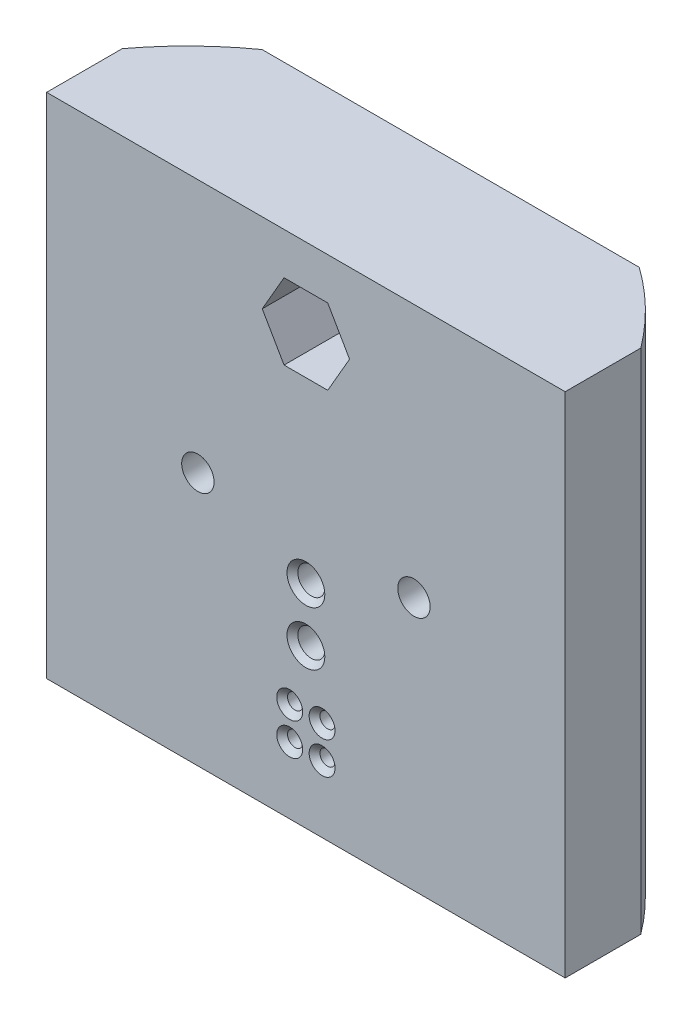
SolidWorks part; units mm, degrees
ref_plane "Front Plane" through (0, 0, 0) normal (0, 0, 1) x (1, 0, 0)
ref_plane "Top Plane" through (0, 0, 0) normal (0, 1, 0) x (1, 0, 0)
ref_plane "Right Plane" through (0, 0, 0) normal (1, 0, 0) x (0, 0, -1)
sketch "Sketch1" plane through (0, 0, 0) normal (0, 0, 1) x (1, 0, 0)
  line L0 (-2.275, -128.15) -> (-2.275, -128.6)
  line L1 (2.275, -128.15) -> (2.275, -128.6)
  line L2 (-2.275, -133.15) -> (-2.275, -134.025)
  line L3 (2.275, -133.15) -> (2.275, -134.025)
  line L11 (-2.275, -128.15) -> (2.275, -128.15)
  line L12 (2.275, -128.15) -> (2.275, -123.6)
  line L13 (2.275, -123.6) -> (-2.275, -123.6)
  line L14 (-2.275, -123.6) -> (-2.275, -128.15)
  line L15 (-2.275, -128.15) -> (2.275, -128.15)
  line L16 (2.275, -128.15) -> (2.275, -123.6)
  line L17 (2.275, -123.6) -> (-2.275, -123.6)
  line L18 (-2.275, -123.6) -> (-2.275, -128.15)
  line L24 (-2.275, -133.15) -> (2.275, -133.15)
  line L25 (2.275, -133.15) -> (2.275, -128.6)
  line L26 (2.275, -128.6) -> (-2.275, -128.6)
  line L27 (-2.275, -128.6) -> (-2.275, -133.15)
  line L28 (-2.275, -133.15) -> (2.275, -133.15)
  line L29 (2.275, -133.15) -> (2.275, -128.6)
  line L30 (2.275, -128.6) -> (-2.275, -128.6)
  line L31 (-2.275, -128.6) -> (-2.275, -133.15)
  line L37 (0, -123.6) -> (0, -142.4) construction
  line L39 (7, -120.5) -> (-7, -120.5)
  line L40 (7, -120.5) -> (7, -145.5)
  line L41 (7, -145.5) -> (-7, -145.5)
  line L42 (-7, -120.5) -> (-7, -145.5)
  line L43 (7, -120.5) -> (-7, -145.5) construction
  line L44 (7, -145.5) -> (-7, -120.5) construction
  line L45 (-1, -142.4) -> (1, -142.4)
  line L46 (1, -142.4) -> (1, -141.625)
  line L47 (1, -141.625) -> (3.8, -141.625)
  line L48 (3.8, -141.625) -> (3.8, -134.025)
  line L49 (3.8, -134.025) -> (-3.8, -134.025)
  line L50 (-3.8, -134.025) -> (-3.8, -141.625)
  line L51 (-3.8, -141.625) -> (-1, -141.625)
  line L52 (-1, -141.625) -> (-1, -142.4)
  line L53 (-1, -142.4) -> (1, -142.4)
  line L54 (1, -142.4) -> (1, -141.625)
  line L55 (1, -141.625) -> (3.8, -141.625)
  line L56 (3.8, -141.625) -> (3.8, -134.025)
  line L57 (3.8, -134.025) -> (-3.8, -134.025)
  line L58 (-3.8, -134.025) -> (-3.8, -141.625)
  line L59 (-3.8, -141.625) -> (-1, -141.625)
  line L60 (-1, -141.625) -> (-1, -142.4)
  circle A0 centre (0, -125.875) radius 1.275
  circle A1 centre (0, -130.875) radius 1.275
  circle A2 centre (-1.5, -139.325) radius 0.65
  circle A3 centre (-1.5, -136.325) radius 0.65
  circle A4 centre (1.5, -136.325) radius 0.65
  circle A5 centre (1.5, -139.325) radius 0.65
  point P25 (0, -133)
  dimension "D4" = 2.55
  dimension "D5" = 1.3
  dimension "D6" = 25
  dimension "D7" = 14
  dimension "D1" = 0.2
  dimension "D2" = 0.2
  dimension "D3" = 0.2
extrude "Boss-Extrude1" add sketch "Sketch1" against normal blind 6.4 contours L39 L42 L41 L40 L60 L59 L58 L57 L31 L18 L17 L16 L29 L56 L55 L54 L53 region at (6.7135, -133, 0)
sketch "Sketch3" plane through (0, 0, 0) normal (0, 0, 1) x (1, 0, 0)
  line L4 (7, -120.5) -> (-7, -120.5)
  line L5 (-7, -120.5) -> (-7, -145.5)
  line L6 (-7, -145.5) -> (7, -145.5)
  line L7 (7, -145.5) -> (7, -120.5)
  line L8 (7, -120.5) -> (-7, -120.5)
  line L9 (-7, -120.5) -> (-7, -145.5)
  line L10 (-7, -145.5) -> (7, -145.5)
  line L11 (7, -145.5) -> (7, -120.5)
  circle A0 centre (-1.5, -139.325) radius 0.7
  circle A1 centre (-1.5, -136.325) radius 0.7
  circle A2 centre (1.5, -136.325) radius 0.7
  circle A3 centre (1.5, -139.325) radius 0.7
  circle A4 centre (0, -130.875) radius 1.25
  circle A5 centre (0, -125.875) radius 1.25
  dimension "D2" = 2.5
  dimension "D3" = 1.4
  dimension "D1" = 0
extrude "Boss-Extrude3" add sketch "Sketch3" along normal blind 7
chamfer "Chamfer1" distance 0.5 angle 45 6 edges at (2.2, -139.325, 7) (-0.8, -139.325, 7) (-0.8, -136.325, 7) (2.2, -136.325, 7) (1.25, -130.875, 7) (1.25, -125.875, 7)
sketch "Sketch4" plane through (0, -145.5, 0) normal (0, -1, 0) x (1, 0, 0)
  line L0 (-7, -6.4) -> (-17.4539, -6.4)
  line L1 (-7, 7) -> (-27.9106, 7)
  line L2 (7, -6.4) -> (17.4539, -6.4)
  line L3 (7, 7) -> (27.9106, 7)
  line L4 (-24, 0) -> (-24, 7)
  line L5 (24, 0) -> (24, 7)
  circle A4 centre (0, 18) radius 30
  arc A5 (-24, 0) -> (24, 0) centre (0, 18) ccw construction
  line M2 (7, -6.4) -> (7, 7)
  line M4 (-7, 7) -> (-7, -6.4)
extrude "Boss-Extrude4" add sketch "Sketch4" against normal up to surface (25 mm away) contours L1 A4 L0 M4 | L2 A4 L3 M2 region at (-14.9215, -145.5, 0.7207) region at (14.9215, -145.5, 0.7207) up to face at (0, -120.5, 0.3)
sketch "Sketch5" plane through (0, -120.5, 0) normal (0, 1, 0) x (1, 0, 0)
  line L2 (17.4539, 6.4) -> (-17.4539, 6.4)
  line L3 (-24, -7) -> (24, -7)
  line L4 (17.4539, 6.4) -> (-17.4539, 6.4)
  line L5 (-24, -7) -> (24, -7)
  line L8 (-24, 0) -> (-24, -7)
  line L9 (-24, 0) -> (-24, -7)
  line L10 (24, -7) -> (24, 0)
  line L11 (24, -7) -> (24, 0)
  arc A2 (-17.4539, 6.4) -> (-24, 0) centre (0, -18) ccw
  arc A3 (24, 0) -> (17.4539, 6.4) centre (0, -18) ccw
  arc A4 (-17.4539, 6.4) -> (-24, 0) centre (0, -18) ccw
  arc A5 (24, 0) -> (17.4539, 6.4) centre (0, -18) ccw
  dimension "D1" = 0
extrude "Boss-Extrude5" add sketch "Sketch5" along normal blind 22
sketch "Sketch6" plane through (0, 0, 7) normal (0, 0, 1) x (1, 0, 0)
  line L0 (0, -98.5) -> (0, -145.5) construction
  line L1 (-24, -98.5) -> (24, -98.5) construction
  line L2 (-24, -145.5) -> (24, -145.5) construction
  circle A0 centre (0, -105.875) radius 2.25
  circle A3 centre (0, -105.875) radius 2.25 construction
  dimension "D2" = 4.5
extrude "Cut-Extrude1" cut sketch "Sketch6" against normal up to next
sketch "Sketch7" plane through (0, 0, 7) normal (0, 0, 1) x (1, 0, 0)
  line L1 (4.0415, -105.875) -> (2.0207, -102.375)
  line L2 (2.0207, -102.375) -> (-2.0207, -102.375)
  line L3 (-2.0207, -102.375) -> (-4.0415, -105.875)
  line L4 (-4.0415, -105.875) -> (-2.0207, -109.375)
  line L5 (-2.0207, -109.375) -> (2.0207, -109.375)
  line L6 (2.0207, -109.375) -> (4.0415, -105.875)
  circle A0 centre (0, -105.875) radius 3.5 construction
  dimension "D1" = 7
extrude "Cut-Extrude2" cut sketch "Sketch7" against normal offset from surface (7.4 mm away) 6 up to face at (2.25, -105.875, -6.4)
sketch "Sketch9" plane through (0, 0, -6.4) normal (0, 0, -1) x (-1, 0, 0)
  line L0 (-24, -122) -> (24, -122) construction
  line L1 (-24, -98.5) -> (-24, -145.5) construction
  line L2 (24, -98.5) -> (24, -145.5) construction
  line L3 (0, -98.5) -> (0, -145.5) construction
  line L4 (-17.4539, -98.5) -> (17.4539, -98.5) construction
  line L5 (-17.4539, -145.5) -> (17.4539, -145.5) construction
  circle A0 centre (-10, -122) radius 1.5
  circle A1 centre (10, -122) radius 1.5
  dimension "D1" = 3
  dimension "D2" = 20
extrude "Cut-Extrude4" cut sketch "Sketch9" against normal up to next
sketch "Sketch10" plane through (0, 0, -6.4) normal (0, 0, -1) x (-1, 0, 0)
  line L0 (0, -98.5) -> (0, -145.5) construction
  line L1 (-10, -125.2332) -> (-7.2, -123.6166)
  line L2 (-7.2, -123.6166) -> (-7.2, -120.3834)
  line L3 (-7.2, -120.3834) -> (-10, -118.7668)
  line L4 (-10, -118.7668) -> (-12.8, -120.3834)
  line L5 (-12.8, -120.3834) -> (-12.8, -123.6166)
  line L6 (-12.8, -123.6166) -> (-10, -125.2332)
  line L7 (-17.4539, -98.5) -> (17.4539, -98.5) construction
  line L8 (-17.4539, -145.5) -> (17.4539, -145.5) construction
  line L9 (12.8, -123.6166) -> (10, -125.2332)
  line L10 (12.8, -120.3834) -> (12.8, -123.6166)
  line L11 (10, -118.7668) -> (12.8, -120.3834)
  line L12 (7.2, -120.3834) -> (10, -118.7668)
  line L13 (7.2, -123.6166) -> (7.2, -120.3834)
  line L14 (10, -125.2332) -> (7.2, -123.6166)
  circle A0 centre (-10, -122) radius 2.8 construction
  dimension "D1" = 5.6
extrude "Cut-Extrude5" cut sketch "Sketch10" against normal offset from surface (7.4 mm away) 6 up to face at (11.5, -122, 7)
